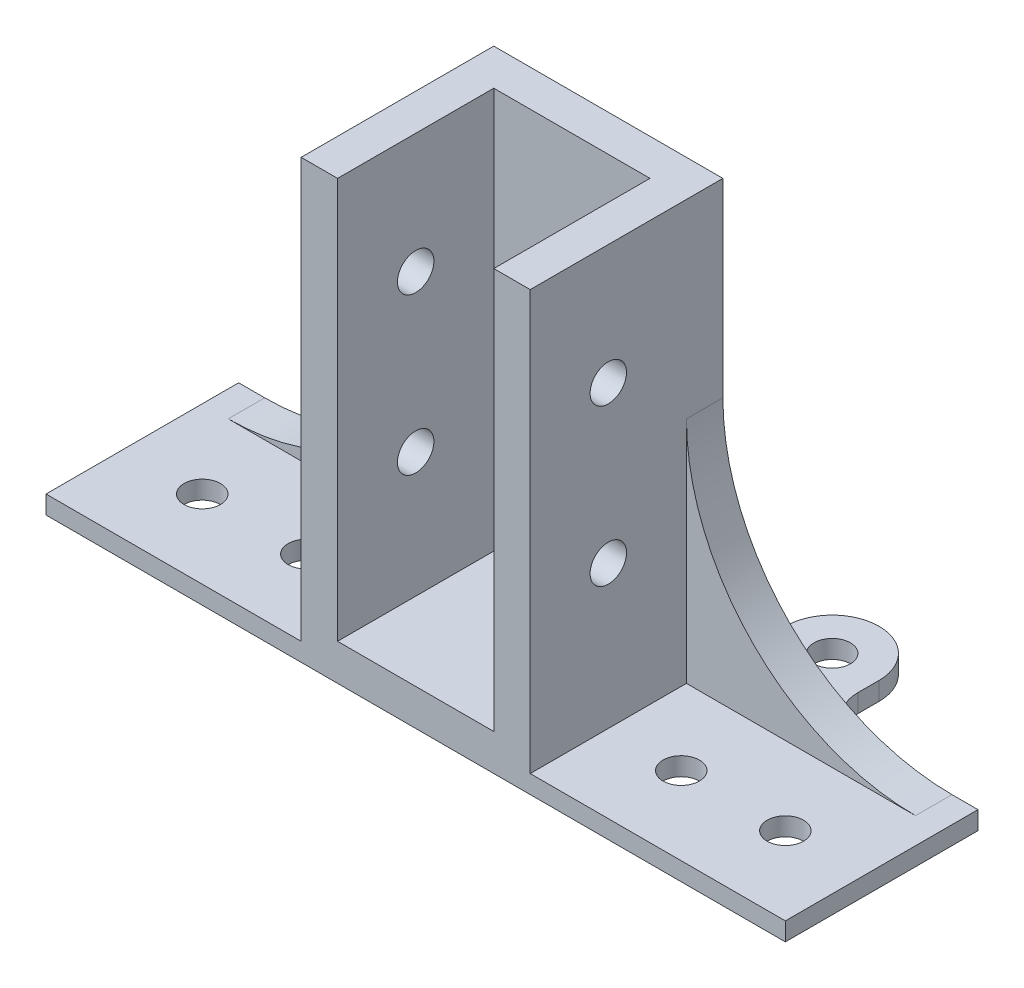
SolidWorks part; units mm, degrees
ref_plane "Front Plane" through (0, 0, 0) normal (0, 0, 1) x (1, 0, 0)
ref_plane "Top Plane" through (0, 0, 0) normal (0, 1, 0) x (1, 0, 0)
ref_plane "Right Plane" through (0, 0, 0) normal (1, 0, 0) x (0, 0, -1)
sketch "Sketch1" plane through (0, 0, 0) normal (0, 0, 1) x (1, 0, 0)
  line L1 (-16.1393, 44.8689) -> (5.8607, 44.8689)
  line L2 (-16.1393, 44.8689) -> (-16.1393, 2.8689)
  line L3 (-16.1393, 2.8689) -> (5.8607, 2.8689)
  line L4 (5.8607, 44.8689) -> (5.8607, 2.8689)
  dimension "D1" = 22
  dimension "D2" = 42
extrude "Boss-Extrude1" add sketch "Sketch1" along normal blind 18.5
sketch "Sketch2" plane through (0, 0, 18.5) normal (0, 0, 1) x (1, 0, 0)
  line L0 (5.8607, 44.8689) -> (-16.1393, 44.8689) construction
  line L1 (-12.6393, 44.8689) -> (2.3607, 44.8689)
  line L2 (-12.6393, 44.8689) -> (-12.6393, 6.3689)
  line L3 (-12.6393, 6.3689) -> (2.3607, 6.3689)
  line L4 (2.3607, 44.8689) -> (2.3607, 6.3689)
  line L5 (5.8607, 2.8689) -> (5.8607, 44.8689) construction
  line L6 (-16.1393, 2.8689) -> (5.8607, 2.8689) construction
  dimension "D1" = 15
  dimension "D2" = 3.5
  dimension "D3" = 3.5
extrude "Cut-Extrude1" cut sketch "Sketch2" against normal blind 15
sketch "Sketch3" plane through (0, 0, 0) normal (0, 0, -1) x (-1, 0, 0)
  line L1 (16.1393, 2.8689) -> (40.6393, 2.8689)
  line L2 (16.1393, 2.8689) -> (16.1393, 4.6189)
  line L3 (16.1393, 4.6189) -> (40.6393, 4.6189)
  line L4 (40.6393, 2.8689) -> (40.6393, 4.6189)
  line L5 (-5.8607, 2.8689) -> (-30.3607, 2.8689)
  line L6 (-5.8607, 2.8689) -> (-5.8607, 4.6189)
  line L7 (-5.8607, 4.6189) -> (-30.3607, 4.6189)
  line L8 (-30.3607, 2.8689) -> (-30.3607, 4.6189)
  dimension "D1" = 24.5
  dimension "D2" = 24.5
  dimension "D3" = 1.75
  dimension "D4" = 1.75
extrude "Boss-Extrude2" add sketch "Sketch3" against normal up to surface (18.5 mm away) up to face at (-5.1393, 24.7439, 18.5)
sketch "Sketch4" plane through (0, 0, 0) normal (0, 0, -1) x (-1, 0, 0)
  line L0 (38.1393, 4.6189) -> (16.1393, 4.6189)
  line L1 (40.6393, 4.6189) -> (16.1393, 4.6189) construction
  line L2 (16.1393, 4.6189) -> (16.1393, 26.6189)
  line L3 (16.1393, 44.8689) -> (16.1393, 4.6189) construction
  line L4 (-27.8607, 4.6189) -> (-5.8607, 4.6189)
  line L5 (-5.8607, 4.6189) -> (-30.3607, 4.6189) construction
  line L6 (-5.8607, 4.6189) -> (-5.8607, 26.6189)
  line L7 (-5.8607, 4.6189) -> (-5.8607, 44.8689) construction
  arc A0 (16.1393, 26.6189) -> (38.1393, 4.6189) centre (38.1393, 26.6189) ccw
  arc A1 (-5.8607, 26.6189) -> (-27.8607, 4.6189) centre (-27.8607, 26.6189) cw
  dimension "D1" = 22
extrude "Boss-Extrude3" add sketch "Sketch4" against normal blind 3.5
sketch "Sketch5" plane through (0, 2.8689, 0) normal (0, -1, 0) x (1, 0, 0)
  line L0 (-40.6393, 0) -> (30.3607, 0) construction
  line L1 (5.8607, 0) -> (-16.1393, 0) construction
  line L2 (14.8607, -6) -> (14.8607, 0)
  line L3 (-25.1393, -6) -> (-25.1393, 0)
  line L4 (-16.1393, -6) -> (-16.1393, 0)
  line L5 (5.8607, -6) -> (5.8607, 0)
  line L6 (14.8607, 0) -> (5.8607, 0)
  line L7 (-16.1393, 0) -> (-25.1393, 0)
  circle A0 centre (10.3607, -6) radius 1.75
  circle A1 centre (-20.6393, -6) radius 1.75
  arc A2 (5.8607, -6) -> (14.8607, -6) centre (10.3607, -6) ccw
  arc A3 (-25.1393, -6) -> (-16.1393, -6) centre (-20.6393, -6) ccw
  point P6 (-5.1393, 0)
  point P7 (-5.1393, 0)
  dimension "D4" = 3.5
  dimension "D1" = 6
  dimension "D2" = 15.5
  dimension "D3" = 15.5
extrude "Boss-Extrude4" add sketch "Sketch5" against normal up to surface (1.75 mm away) up to face at (-33.8893, 4.6189, 8.5833)
sketch "Sketch6" plane through (0, 4.6189, 0) normal (0, 1, 0) x (1, 0, 0)
  line L0 (30.3607, -11) -> (-40.6393, -11) construction
  line L1 (30.3607, -18.5) -> (30.3607, 0) construction
  line L2 (-40.6393, -18.5) -> (-40.6393, 0) construction
  line L3 (5.8607, -18.5) -> (30.3607, -18.5) construction
  circle A0 centre (22.8607, -11) radius 1.75
  circle A1 centre (-33.1393, -11) radius 1.75
  circle A2 centre (12.8607, -11) radius 1.75
  circle A3 centre (-23.1393, -11) radius 1.75
  dimension "D2" = 7.5
  dimension "D3" = 7.5
  dimension "D4" = 3.5
  dimension "D5" = 10
  dimension "D6" = 10
  dimension "D1" = 7.5
extrude "Cut-Extrude2" cut sketch "Sketch6" against normal blind 10
fillet "Fillet1" radius 4 4 edges at (-25.1393, 3.7439, 0) (-16.1393, 3.7439, 0)
sketch "Sketch7" plane through (-16.1393, 0, 0) normal (-1, 0, 0) x (0, 0, 1)
  line L0 (11, 44.8689) -> (11, 4.6189) construction
  line L1 (18.5, 44.8689) -> (0, 44.8689) construction
  line L2 (18.5, 4.6189) -> (0, 4.6189) construction
  line L3 (18.5, 44.8689) -> (18.5, 4.6189) construction
  line L4 (3.5, 6.3689) -> (18.5, 6.3689) construction
  circle A0 centre (11, 33.3689) radius 1.75
  circle A1 centre (11, 18.3689) radius 1.75
  dimension "D2" = 3.5
  dimension "D1" = 7.5
  dimension "D3" = 15
  dimension "D4" = 12
extrude "Cut-Extrude3" cut sketch "Sketch7" against normal blind 28
sketch "Sketch8" plane through (0, 0, 0) normal (0, 0, -1) x (-1, 0, 0)
  line L0 (5.1393, 44.8689) -> (5.1393, 2.8689) construction
  line L1 (-5.8607, 44.8689) -> (16.1393, 44.8689) construction
  line L2 (12.1393, 2.8689) -> (-1.8607, 2.8689) construction
  line L3 (12.6393, 6.3689) -> (-2.3607, 6.3689) construction
  circle A0 centre (5.1393, 33.3689) radius 1.75
  circle A1 centre (5.1393, 18.3689) radius 1.75
  dimension "D1" = 15
  dimension "D2" = 12
  dimension "D3" = 3.5
extrude "Cut-Extrude4" cut sketch "Sketch8" against normal blind 28
